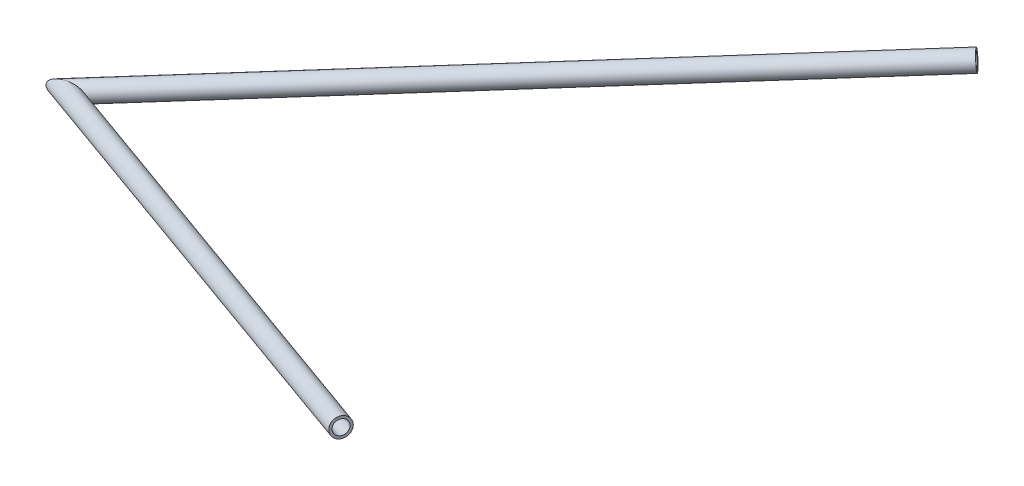
SolidWorks part; units mm, degrees
note: '?' marks a value the reader was unsure of.
material "AISI 4340 Steel, annealed"
ref_plane "Front Plane" through (0, 0, 0) normal (0, 0, 1) x (1, 0, 0)
ref_plane "Top Plane" through (0, 0, 0) normal (0, 1, 0) x (1, 0, 0)
ref_plane "Right Plane" through (0, 0, 0) normal (1, 0, 0) x (0, 0, -1)
sketch3d "reference sketch"
  line L2 (-52, -175.4, 0) -> (435, -124.6, -440.9449)
  line L3 (435, -124.6, 206.8) -> (-52, -175.4, 0)
sketch3d "3DSketch2"
  line L0 (435, -124.6, 206.8) -> (-52, -175.4, 0) construction
  line L1 (-52, -175.4, 0) -> (435, -124.6, -440.9449) construction
  line L2 (435, -124.6, 206.8) -> (-52, -175.4, 0)
  line L3 (-52, -175.4, 0) -> (435, -124.6, -440.9449)
other "Pipe standard s40 PIPE 1 SCH 40(1)" corner treatment miter
ref_plane "Plane1" through (-52, -175.4, 0) normal (0.7391, 0.0771, -0.6692) x (-0.6512, -0.1722, -0.7391)
sketch "Sketch1" plane through (-52, -175.4, 0) normal (0.7391, 0.0771, -0.6692) x (-0.6512, -0.1722, -0.7391)
  circle A0 centre (0, 0) radius 6.985
  circle A1 centre (0, 0) radius 9.525
  point P3 (0, 0)
  dimension "D1" = 19.05
  dimension "D2" = 2.54
ref_axis "pivot axis" through (435, -124.6, 206.8) along (0, 0, -1)?
ref_point "upright mounting point"
